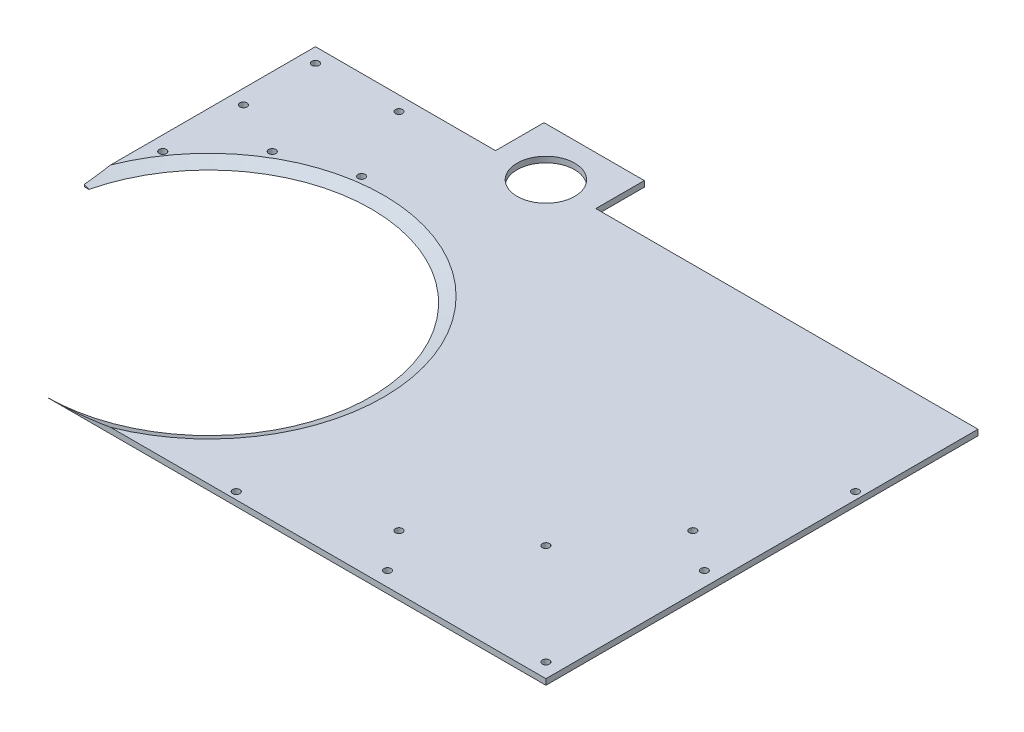
SolidWorks part; units mm, degrees
ref_plane "Front Plane" through (0, 0, 0) normal (0, 0, 1) x (1, 0, 0)
ref_plane "Top Plane" through (0, 0, 0) normal (0, 1, 0) x (1, 0, 0)
ref_plane "Right Plane" through (0, 0, 0) normal (1, 0, 0) x (0, 0, -1)
sketch "Sketch1" plane through (0, 0, 0) normal (0, 1, 0) x (1, 0, 0)
  line L1 (0, 0) -> (381, 0)
  line L2 (0, 0) -> (0, 381)
  line L3 (0, 381) -> (381, 381)
  line L4 (381, 0) -> (381, 381)
  line L5 (0, 381) -> (-203.2, 381)
  line L6 (0, 381) -> (0, 0)
  line L7 (0, 0) -> (-203.2, 0)
  line L8 (-203.2, 381) -> (-203.2, 0)
  arc A0 (381, 381) -> (0, 0) centre (0, 381) cw
  circle A1 centre (39.2386, 142.9117) radius 139.7
  circle A2 centre (0, 381) radius 101.6
  circle A3 centre (196.7476, 241.3) radius 139.7
  circle A4 centre (86.3584, 155.6826) radius 139.7
  circle A5 centre (-59.7956, 143.4044) radius 143.4044
  dimension "D1" = 381
  dimension "D2" = 381
  dimension "D3" = 203.2
sketch "Sketch2" plane through (0, 0, 0) normal (0, 1, 0) x (1, 0, 0)
  line L0 (-203.2, 381) -> (-44.423, 381)
  line L1 (44.0206, 381) -> (381, 381)
  line L2 (-203.2, 381) -> (-203.2, 0)
  line L3 (-203.2, 0) -> (381, 0)
  line L4 (381, 381) -> (381, 0)
  line L6 (-44.423, 381) -> (-44.423, 423.7475)
  line L7 (-44.423, 423.7475) -> (44.0206, 423.7475)
  line L8 (44.0206, 381) -> (44.0206, 423.7475)
extrude "Boss-Extrude1" add sketch "Sketch2" along normal blind 5.08 from offset 33.02
sketch "Sketch4" plane through (0, 33.02, 0) normal (0, -1, 0) x (1, 0, 0)
  circle A0 centre (0, -381) radius 25.4
  dimension "D1" = 50.8
extrude "Cut-Extrude1" cut sketch "Sketch4" against normal blind 50.8
extrude "Cut-Extrude5" cut sketch "Sketch1" along normal blind 38.1 from offset 5.08
chamfer "Chamfer1" distance 5.08 angle 65 1 edges at (41.6067, 38.1, -244.8067)
sketch "Sketch6" plane through (-203.2, 0, 0) normal (-1, 0, 0) x (0, 0, 1)
  line L1 (-143.4044, 33.02) -> (-177.1864, 33.02)
  line L2 (-143.4044, 33.02) -> (-143.4044, 47.4524)
  line L3 (-143.4044, 47.4524) -> (-177.1864, 47.4524)
  line L4 (-177.1864, 33.02) -> (-177.1864, 47.4524)
  dimension "D1" = 33.782
extrude "Cut-Extrude7" cut sketch "Sketch6" against normal blind 25.4
sketch "Sketch7" plane through (0, 38.1, 0) normal (0, 1, 0) x (1, 0, 0)
  line L0 (-2.8464, 0) -> (381, 0) construction
  line L1 (381, 0) -> (381, 381) construction
  circle A0 centre (368.3, 152.4) radius 3.175
  circle A1 centre (374.65, 279.4) radius 3.175
  circle A2 centre (332.74, 177.8) radius 3.175
  circle A3 centre (279.4, 101.6) radius 3.175
  circle A4 centre (101.6, 6.35) radius 3.175
  circle A5 centre (203.2, 48.26) radius 3.175
  circle A6 centre (228.6, 12.7) radius 3.175
  circle A7 centre (368.3, 12.7) radius 3.175
  dimension "D1" = 6.35
  dimension "D2" = 12.7
  dimension "D3" = 12.7
  dimension "D4" = 12.7
  dimension "D5" = 152.4
  dimension "D6" = 6.35
  dimension "D7" = 279.4
  dimension "D8" = 48.26
  dimension "D9" = 177.8
  dimension "D10" = 101.6
  dimension "D11" = 101.6
  dimension "D12" = 48.26
  dimension "D13" = 177.8
  dimension "D14" = 279.4
  dimension "D15" = 6.35
  dimension "D16" = 12.7
  dimension "D17" = 152.4
extrude "Cut-Extrude8" cut sketch "Sketch7" against normal blind 5.08
sketch "Sketch8" plane through (0, 38.1, 0) normal (0, 1, 0) x (1, 0, 0)
  line L0 (-44.423, 381) -> (-203.2, 381) construction
  line L1 (-203.2, 381) -> (-203.2, 200.3536) construction
  circle A0 centre (-190.5, 368.3) radius 3.175
  circle A1 centre (-116.84, 368.3) radius 3.175
  circle A2 centre (-83.82, 302.26) radius 3.175
  circle A3 centre (-142.24, 281.94) radius 3.175
  circle A4 centre (-190.5, 304.8) radius 3.175
  circle A5 centre (-190.5, 233.68) radius 3.175
  dimension "D1" = 6.35
  dimension "D2" = 12.7
  dimension "D3" = 12.7
  dimension "D4" = 12.7
  dimension "D5" = 86.36
  dimension "D6" = 119.38
  dimension "D7" = 78.74
  dimension "D8" = 60.96
  dimension "D9" = 99.06
  dimension "D10" = 12.7
  dimension "D11" = 147.32
  dimension "D12" = 12.7
  dimension "D13" = 76.2
extrude "Cut-Extrude9" cut sketch "Sketch8" against normal blind 5.08
